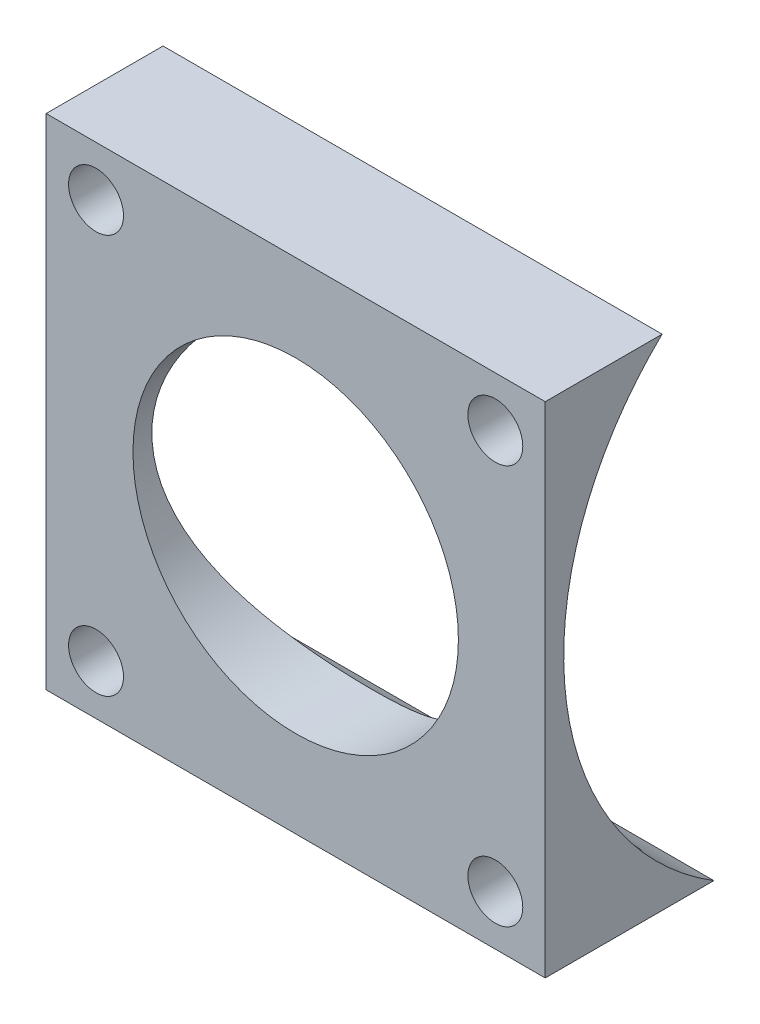
SolidWorks part; units mm, degrees
ref_plane "Front Plane" through (0, 0, 0) normal (0, 0, 1) x (1, 0, 0)
ref_plane "Top Plane" through (0, 0, 0) normal (0, 1, 0) x (1, 0, 0)
ref_plane "Right Plane" through (0, 0, 0) normal (1, 0, 0) x (0, 0, -1)
sketch "Sketch1" plane through (0, 0, 0) normal (0, 0, 1) x (1, 0, 0)
  line L1 (-25, 23) -> (25, 23)
  line L2 (-25, 23) -> (-25, -27)
  line L3 (-25, -27) -> (25, -27)
  line L4 (25, 23) -> (25, -27)
  line L5 (-25, 23) -> (25, -27) construction
  line L6 (-25, -27) -> (25, 23) construction
  circle A0 centre (0, -2) radius 16.3
  circle A1 centre (-20, 18) radius 2.75
  circle A2 centre (20, 18) radius 2.75
  circle A3 centre (20, -22) radius 2.75
  circle A4 centre (-20, -22) radius 2.75
  point P0 (0, -2)
  dimension "D4" = 32.6
  dimension "D6" = 5.5
  dimension "D1" = 2
  dimension "D2" = 50
  dimension "D3" = 50
  dimension "D5" = 20
  dimension "D7" = 20
  dimension "D9" = 20
  dimension "D10" = 20
extrude "Boss-Extrude1" add sketch "Sketch1" along normal blind 33.6
sketch "Sketch2" plane through (0, 0, 0) normal (1, 0, 0) x (0, 0, -1)
  circle A0 centre (0, 0) radius 31.75
  dimension "D1" = 63.5
extrude "Cut-Extrude1" cut sketch "Sketch2" against normal through all and the other way through all
